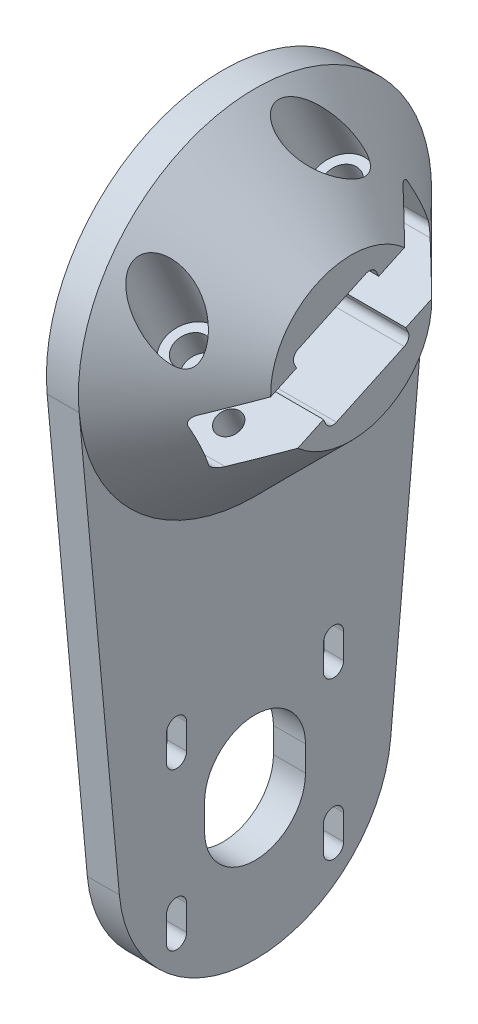
SolidWorks part; units mm, degrees
ref_plane "Front Plane" through (0, 0, 0) normal (0, 0, 1) x (1, 0, 0)
ref_plane "Top Plane" through (0, 0, 0) normal (0, 1, 0) x (1, 0, 0)
ref_plane "Right Plane" through (0, 0, 0) normal (1, 0, 0) x (0, 0, -1)
sketch "Sketch1" plane through (0, 0, 0) normal (1, 0, 0) x (0, 0, -1)
  line L0 (4.3532, 11.9603) -> (-11.9603, 4.3532)
  line L1 (4.3532, 11.9603) -> (11.9603, -4.3532)
  line L2 (-11.9603, 4.3532) -> (-4.3532, -11.9603)
  line L3 (11.9603, -4.3532) -> (-4.3532, -11.9603)
  line L4 (4.3532, 11.9603) -> (-4.3532, -11.9603) construction
  line L5 (-11.9603, 4.3532) -> (11.9603, -4.3532) construction
  line L6 (0, 0) -> (0, -85) construction
  line L7 (-34.8534, -3.2) -> (-26.8869, -89.9686)
  line L8 (26.8869, -89.9686) -> (34.8534, -3.2)
  line L9 (0, -85) -> (0, -103.9417) construction
  arc A0 (34.8534, -3.2) -> (-34.8534, -3.2) centre (0, 0) ccw
  arc A1 (-26.8869, -89.9686) -> (26.8869, -89.9686) centre (0, -87.5) ccw
  dimension "D1" = 2.5
  dimension "D2" = 70
  dimension "D6" = 85
  dimension "D7" = 27
  dimension "D8" = 0
  dimension "D3" = 18
  dimension "D4" = 18
  dimension "D5" = 25
extrude "Boss-Extrude1" add sketch "Sketch1" along normal blind 6.35 contours L7 A0 L1 L3 L2 L0 region at (0, -38.184, 0)
sketch "Sketch17" plane through (0, 0, 0) normal (-1, 0, 0) x (0, 0, 1)
  line L2 (-34.8534, -3.2) -> (-26.8869, -89.9686)
  line L3 (26.8869, -89.9686) -> (34.8534, -3.2)
  line L4 (-34.8534, -3.2) -> (-26.8869, -89.9686)
  line L6 (26.8869, -89.9686) -> (34.8534, -3.2)
  arc A2 (-26.8869, -89.9686) -> (26.8869, -89.9686) centre (0, -87.5) ccw
  arc A3 (-26.8869, -89.9686) -> (26.8869, -89.9686) centre (0, -87.5) ccw
  arc A4 (34.8534, -3.2) -> (-34.8534, -3.2) centre (0, 0) ccw
  arc A8 (34.8534, -3.2) -> (-34.8534, -3.2) centre (0, 0) ccw
  dimension "D1" = 0
sketch "Sketch20" plane through (6.35, 0, 0) normal (1, 0, 0) x (0, 0, -1)
  circle A0 centre (0, 0) radius 35
extrude "Boss-Extrude5" add sketch "Sketch20" along normal blind 19.05
sketch "Sketch21" plane through (0, 0, 0) normal (-1, 0, 0) x (0, 0, 1)
  line L0 (-24.435, 4.3878) -> (-10.8404, -1.9515)
  line L1 (11.9603, 4.3532) -> (4.3532, -11.9603) construction
  line L3 (-4.3532, 11.9603) -> (-11.9603, -4.3532) construction
  line L4 (-4.3532, 11.9603) -> (11.9603, 4.3532) construction
  line L5 (11.9603, 4.3532) -> (10.8404, 1.9515)
  line L7 (-4.3532, 11.9603) -> (-5.4731, 9.5586)
  line L8 (-4.3532, 11.9603) -> (11.9603, 4.3532)
  line L9 (-21.7514, 10.1428) -> (-25.3766, 11.8333) construction
  line L10 (19.0678, -15.8979) -> (5.4731, -9.5586)
  line L11 (19.0678, -15.8979) -> (24.435, -4.3878)
  line L12 (-24.435, 4.3878) -> (-19.0678, 15.8979)
  line L13 (24.435, -4.3878) -> (10.8404, 1.9515)
  line L16 (4.3532, -11.9603) -> (5.4731, -9.5586)
  line L17 (-11.9603, -4.3532) -> (-10.8404, -1.9515)
  line L18 (11.9603, 4.3532) -> (-4.3532, 11.9603)
  line L21 (-10.8404, -1.9515) -> (-11.9603, -4.3532)
  line L24 (-10.8404, -1.9515) -> (-24.435, 4.3878)
  line L27 (-5.4731, 9.5586) -> (-4.3532, 11.9603)
  line L29 (-5.4731, 9.5586) -> (-19.0678, 15.8979)
  line L30 (5.4731, -9.5586) -> (4.3532, -11.9603)
  line L31 (10.8404, 1.9515) -> (11.9603, 4.3532)
  line M13 (-11.9603, -4.3532) -> (-4.3532, 11.9603)
  line M14 (-4.3532, 11.9603) -> (11.9603, 4.3532)
  line M15 (11.9603, 4.3532) -> (4.3532, -11.9603)
  line M16 (4.3532, -11.9603) -> (-11.9603, -4.3532)
  dimension "D1" = 15
  dimension "D2" = 12.7
extrude "Cut-Extrude14" cut sketch "Sketch21" against normal through all contours L29 L12 L0 M13 | M13 M16 M15 M14 | L11 L13 L10 M15 region at (0, 6.9732, -14.9541) region at (0, 0, 0) region at (0, -6.9732, 14.9541)
chamfer "Chamfer1" distance 19.05 angle 45 1 edges at (25.4, 0, -35)
sketch "Sketch22" plane through (0, 5.7551, 2.6836) normal (0, -0.9063, -0.4226) x (-1, 0, 0)
  line L0 (-25.4, -9) -> (0, -9) construction
  line L1 (-25.4, -9) -> (-25.4, -14.6315) construction
  circle A0 centre (-13.4, -16.5) radius 3.175
  dimension "D2" = 12
  dimension "D3" = 6.35
  dimension "D1" = 7.5
extrude "Cut-Extrude15" cut sketch "Sketch22" against normal through all
ref_plane "Plane1" through (0, 10.2866, 4.7967) normal (0, -0.9063, -0.4226) x (-1, 0, 0)
sketch "Sketch24" plane through (0, 10.2866, 4.7967) normal (0, -0.9063, -0.4226) x (-1, 0, 0)
  circle A0 centre (-13.4, -16.5) radius 5
  dimension "D1" = 10
extrude "Cut-Extrude16" cut sketch "Sketch24" against normal through all
sketch "Sketch25" plane through (0, -5.7551, -2.6836) normal (0, 0.9063, 0.4226) x (1, 0, 0)
  circle A0 centre (13.4, -16.5) radius 3.175 construction
  circle A1 centre (13.4, -16.5) radius 3.175
  circle A2 centre (13.4, -16.5) radius 2.3813
  dimension "D1" = 0.7937
extrude "Cut-Extrude17" cut sketch "Sketch25" against normal blind 10 contours A2 region at (13.4, -12.7283, 12.2705)
ref_plane "Plane2" through (0, 0, 0) normal (0, 0.4226, -0.9063) x (-1, 0, 0)
mirror "Mirror1" about plane through (0, 0, 0) normal (0, 0.4226, -0.9063) of "Cut-Extrude15", "Cut-Extrude17", "Cut-Extrude16"
sketch "Sketch19" plane through (6.35, 0, 0) normal (1, 0, 0) x (0, 0, -1)
  line L0 (0, -87.5) -> (0, -82.5)
  line L1 (0, -82.5) -> (15.5563, -66.9437) construction
  line L2 (15.5563, -71.9437) -> (15.5563, -66.9437) construction
  line L3 (13.5563, -71.9437) -> (13.5563, -66.9437)
  line L4 (17.5563, -71.9437) -> (17.5563, -66.9437)
  line L5 (-10, -87.5) -> (-10, -82.5)
  line L6 (10, -87.5) -> (10, -82.5)
  line L7 (0, -85) -> (7.4061, -85) construction
  line L8 (15.5563, -71.9437) -> (0, -87.5) construction
  line L9 (17.5563, -98.0563) -> (17.5563, -103.0563)
  line L10 (13.5563, -98.0563) -> (13.5563, -103.0563)
  line L11 (-17.5563, -71.9437) -> (-17.5563, -66.9437)
  line L12 (-13.5563, -71.9437) -> (-13.5563, -66.9437)
  line L13 (-13.5563, -98.0563) -> (-13.5563, -103.0563)
  line L14 (-17.5563, -98.0563) -> (-17.5563, -103.0563)
  line L15 (-15.5563, -71.9437) -> (0, -87.5) construction
  line L16 (0, -87.5) -> (-15.5563, -103.0563) construction
  line L17 (0, -87.5) -> (15.5563, -103.0563) construction
  arc A2 (-10, -87.5) -> (10, -87.5) centre (0, -87.5) ccw
  arc A3 (17.5563, -103.0563) -> (13.5563, -103.0563) centre (15.5563, -103.0563) cw
  arc A4 (13.5563, -98.0563) -> (17.5563, -98.0563) centre (15.5563, -98.0563) cw
  arc A6 (17.5563, -66.9437) -> (13.5563, -66.9437) centre (15.5563, -66.9437) ccw
  arc A7 (13.5563, -71.9437) -> (17.5563, -71.9437) centre (15.5563, -71.9437) ccw
  arc A8 (-17.5563, -66.9437) -> (-13.5563, -66.9437) centre (-15.5563, -66.9437) cw
  arc A9 (10, -82.5) -> (-10, -82.5) centre (0, -82.5) ccw
  arc A10 (-13.5563, -71.9437) -> (-17.5563, -71.9437) centre (-15.5563, -71.9437) cw
  arc A11 (-13.5563, -98.0563) -> (-17.5563, -98.0563) centre (-15.5563, -98.0563) ccw
  arc A13 (-17.5563, -103.0563) -> (-13.5563, -103.0563) centre (-15.5563, -103.0563) ccw
  point P8 (0, -85)
  dimension "D1" = 82.5
  dimension "D3" = 22
  dimension "D5" = 4
  dimension "D6" = 5
  dimension "D4" = 4
  dimension "D2" = 5
  dimension "D7" = 45
extrude "Cut-Extrude18" cut sketch "Sketch19" against normal blind 10 contours L6 A9 L5 A2 | A10 L12 A8 L11 | L14 A13 L13 A11 | A4 L10 A3 L9 | L4 A6 L3 A7 region at (6.35, -85, 9.6798) region at (6.35, -100.5563, -15.5563) region at (6.35, -69.4437, 15.5563) region at (6.35, -100.5563, 15.5563)
mirror "Mirror2" about plane through (0, 0, 0) normal (1, 0, 0) of bodies 126
delete or keep bodies "Body-Delete/Keep 1" type delete bodies bodies 127
chamfer "Chamfer2" distance 2.5 angle 45 8 edges at (0, -73.9437, 15.5563) (0, -69.4437, 13.5563) (0, -64.9437, 15.5563) (0, -69.4437, 17.5563) (0, -73.9437, -15.5563) (0, -69.4437, -17.5563) (0, -69.4437, -13.5563) (0, -64.9437, -15.5563)
sketch "Sketch26" plane through (0, 0, 0) normal (-1, 0, 0) x (0, 0, 1)
  line L0 (11.7635, -84.8709) -> (27.7421, -5.5914)
  line L1 (0, 0) -> (0, -82.5) construction
  circle A0 centre (0, -82.5) radius 12
  circle A1 centre (0, 0) radius 28.3
  dimension "D1" = 24
  dimension "D2" = 56.6
fillet "Fillet1" radius 1.5875 8 edges at (12.7, -4.3532, -11.9603) (8.2621, 4.3878, -24.435) (12.7, 11.9603, -4.3532) (8.2621, 15.8979, -19.0678) (8.2621, -4.3878, 24.435) (12.7, 4.3532, 11.9603) (12.7, -11.9603, 4.3532) (8.2621, -15.8979, 19.0678)
sketch "Sketch27" plane through (6.35, 0, 0) normal (1, 0, 0) x (0, 0, -1)
  arc A0 (-26.8869, -89.9686) -> (26.8869, -89.9686) centre (0, -87.5) ccw construction
  arc A1 (34.8534, -3.2) -> (-34.8534, -3.2) centre (0, 0) ccw construction
  point P0 (0, -114.5)
  point P1 (0, 35)
  point P5 (-34.8534, -3.2)
  point P9 (35, 0)
equation "\".75i\"=14.27"
